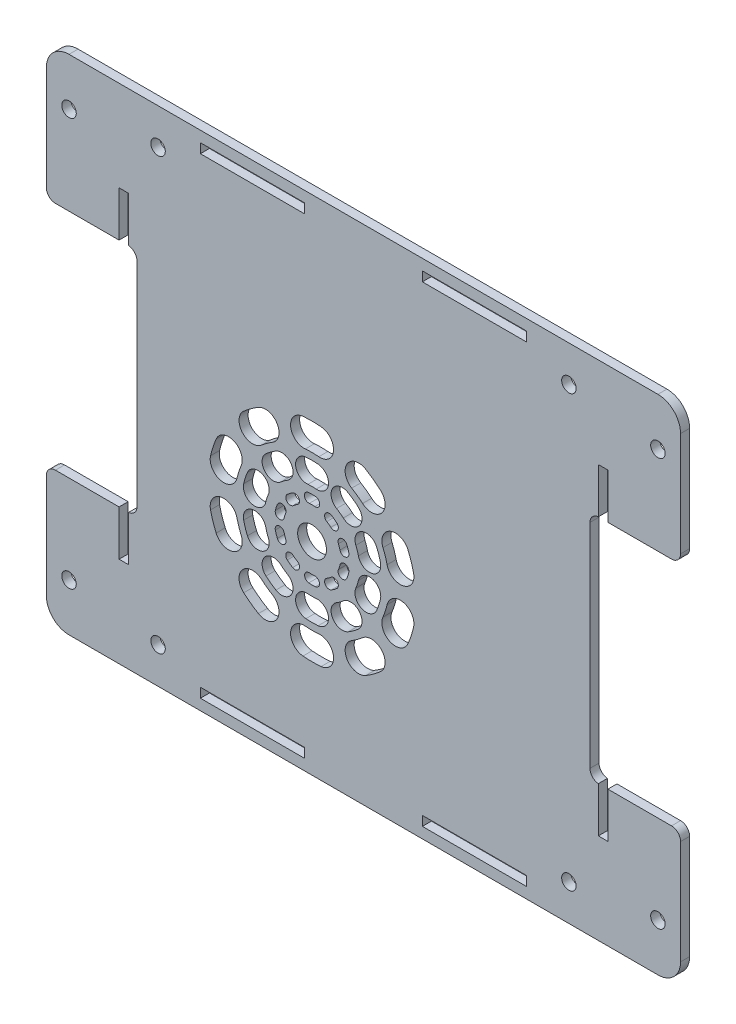
SolidWorks part; units mm, degrees
ref_plane "前视基准面" through (0, 0, 0) normal (0, 0, 1) x (1, 0, 0)
ref_plane "上视基准面" through (0, 0, 0) normal (0, 1, 0) x (1, 0, 0)
ref_plane "右视基准面" through (0, 0, 0) normal (1, 0, 0) x (0, 0, -1)
sketch "草图1" plane through (0, 0, 0) normal (0, 0, 1) x (1, 0, 0)
  line L1 (-70, 55.5) -> (70, 55.5)
  line L2 (-70, 55.5) -> (-70, -55.5)
  line L3 (-70, -55.5) -> (70, -55.5)
  line L4 (70, 55.5) -> (70, -55.5)
  line L5 (-70, 55.5) -> (70, -55.5) construction
  line L6 (-70, -55.5) -> (70, 55.5) construction
  point P0 (0, 0)
  dimension "D1" = 111
  dimension "D2" = 140
extrude "凸台-拉伸1" add sketch "草图1" along normal blind 2
sketch "草图2" plane through (0, 0, 0) normal (0, 0, -1) x (-1, 0, 0)
  circle A0 centre (-45.35, -47.55) radius 1.6
  circle A1 centre (45.35, -47.55) radius 1.6
  circle A2 centre (45.35, 47.55) radius 1.6
  circle A3 centre (-45.35, 47.55) radius 1.6
  dimension "D2" = 3.2
  dimension "D1" = 45.35
  dimension "D3" = 47.55
  dimension "D4" = 2
  dimension "D5" = 2
extrude "切除-拉伸1" cut sketch "草图2" against normal through all
sketch "草图3" plane through (0, 0, 0) normal (0, 0, -1) x (-1, 0, 0)
  line L0 (0, 0) -> (0, -29.5446) construction
  line L1 (0, 0) -> (30.314, 0) construction
  line L3 (-53.95, 35.5) -> (-51.85, 35.5)
  line L4 (-53.95, 35.5) -> (-53.95, 12.5)
  line L5 (-53.95, 12.5) -> (-51.85, 12.5)
  line L6 (-51.85, 35.5) -> (-51.85, 12.5)
  line L7 (-53.95, -12.5) -> (-51.85, -12.5)
  line L8 (-53.95, -12.5) -> (-53.95, -35.5)
  line L9 (-53.95, -35.5) -> (-51.85, -35.5)
  line L10 (-51.85, -12.5) -> (-51.85, -35.5)
  line L11 (70, -55.5) -> (-70, -55.5) construction
  line L12 (-70, 55.5) -> (70, 55.5) construction
  line L13 (51.85, -12.5) -> (51.85, -35.5)
  line L14 (53.95, -35.5) -> (51.85, -35.5)
  line L15 (53.95, -12.5) -> (53.95, -35.5)
  line L16 (53.95, -12.5) -> (51.85, -12.5)
  line L17 (51.85, 35.5) -> (51.85, 12.5)
  line L18 (53.95, 12.5) -> (51.85, 12.5)
  line L19 (53.95, 35.5) -> (53.95, 12.5)
  line L20 (53.95, 35.5) -> (51.85, 35.5)
  line L21 (-70, -55.5) -> (-70, 55.5) construction
  line L22 (-36, -51) -> (-13, -51)
  line L23 (-36, -51) -> (-36, -53.1)
  line L24 (-36, -53.1) -> (-13, -53.1)
  line L25 (-13, -51) -> (-13, -53.1)
  line L26 (13, -51) -> (36, -51)
  line L27 (13, -51) -> (13, -53.1)
  line L28 (13, -53.1) -> (36, -53.1)
  line L29 (36, -51) -> (36, -53.1)
  line L30 (70, 55.5) -> (70, -55.5) construction
  line L31 (36, 51) -> (36, 53.1)
  line L32 (13, 53.1) -> (36, 53.1)
  line L33 (13, 51) -> (13, 53.1)
  line L34 (13, 51) -> (36, 51)
  line L35 (-13, 51) -> (-13, 53.1)
  line L36 (-36, 53.1) -> (-13, 53.1)
  line L37 (-36, 51) -> (-36, 53.1)
  line L38 (-36, 51) -> (-13, 51)
  point P16 (-52.9, 35.5)
  dimension "D1" = 2.1
  dimension "D2" = 2.1
  dimension "D3" = 51.85
  dimension "D4" = 23
  dimension "D5" = 23
  dimension "D6" = 20
  dimension "D7" = 20
  dimension "D8" = 51
  dimension "D9" = 2.1
  dimension "D10" = 2.1
  dimension "D11" = 23
  dimension "D12" = 23
  dimension "D13" = 34
  dimension "D14" = 34
extrude "切除-拉伸2" cut sketch "草图3" against normal through all
sketch "草图4" plane through (0, 0, 2) normal (0, 0, 1) x (1, 0, 0)
  line L0 (-70, -55.5) -> (70, -55.5) construction
  line L2 (-13.0931, 9.1239) -> (-11.35, -10.8) construction
  line L3 (-11.35, -10.8) -> (-9.6069, 9.1239) construction
  line L4 (-11.35, -10.8) -> (-11.35, 9.2) construction
  line L5 (-70, 55.5) -> (-70, -55.5) construction
  line L7 (-11.35, -10.8) -> (8.65, -10.8) construction
  circle A0 centre (-11.35, -10.8) radius 20 construction
  arc A1 (-13.0931, 9.1239) -> (-9.6069, 9.1239) centre (-11.35, -10.8) cw construction
  arc A2 (-9.3454, 12.1125) -> (-13.3546, 12.1125) centre (-11.35, -10.8) ccw
  arc A3 (-9.8684, 6.1353) -> (-12.8316, 6.1353) centre (-11.35, -10.8) ccw
  arc A4 (-9.8684, 6.1353) -> (-9.3454, 12.1125) centre (-9.6069, 9.1239) ccw
  arc A5 (-13.3546, 12.1125) -> (-12.8316, 6.1353) centre (-13.0931, 9.1239) ccw
  arc A6 (-10.217, 2.1505) -> (-12.483, 2.1505) centre (-11.35, -10.8) ccw construction
  arc A7 (-9.9991, 4.641) -> (-12.7009, 4.641) centre (-11.35, -10.8) ccw
  arc A8 (-10.4349, -0.34) -> (-12.2651, -0.34) centre (-11.35, -10.8) ccw
  arc A9 (-10.4349, -0.34) -> (-9.9991, 4.641) centre (-10.217, 2.1505) ccw
  arc A10 (-12.7009, 4.641) -> (-12.2651, -0.34) centre (-12.483, 2.1505) ccw
  arc A11 (-12.0472, -2.8304) -> (-10.6528, -2.8304) centre (-11.35, -10.8) cw construction
  arc A12 (-10.5656, -1.8342) -> (-12.1344, -1.8342) centre (-11.35, -10.8) ccw
  arc A13 (-10.7399, -3.8266) -> (-11.9601, -3.8266) centre (-11.35, -10.8) ccw
  arc A14 (-10.7399, -3.8266) -> (-10.5656, -1.8342) centre (-10.6528, -2.8304) ccw
  arc A15 (-12.1344, -1.8342) -> (-11.9601, -3.8266) centre (-12.0472, -2.8304) ccw
  arc A16 (-1.0492, 6.3433) -> (1.7712, 4.2942) centre (-11.35, -10.8) cw construction
  arc A21 (3.7394, 6.5583) -> (0.4959, 8.9148) centre (-11.35, -10.8) ccw
  arc A26 (-0.197, 2.0301) -> (-2.5944, 3.7718) centre (-11.35, -10.8) ccw
  arc A31 (-0.197, 2.0301) -> (3.7394, 6.5583) centre (1.7712, 4.2942) ccw
  arc A36 (0.4959, 8.9148) -> (-2.5944, 3.7718) centre (-1.0492, 6.3433) ccw
  arc A41 (-2.8212, -0.9888) -> (-4.6545, 0.3432) centre (-11.35, -10.8) ccw construction
  arc A46 (-1.1811, 0.898) -> (-3.3669, 2.4861) centre (-11.35, -10.8) ccw
  arc A51 (-4.4614, -2.8755) -> (-5.9421, -1.7997) centre (-11.35, -10.8) ccw
  arc A56 (-4.4614, -2.8755) -> (-1.1811, 0.898) centre (-2.8212, -0.9888) ccw
  arc A62 (-3.3669, 2.4861) -> (-5.9421, -1.7997) centre (-4.6545, 0.3432) ccw
  arc A63 (-7.5793, -4.5246) -> (-6.5469, -5.2747) centre (-11.35, -10.8) cw construction
  arc A64 (-5.8909, -4.52) -> (-7.0643, -3.6674) centre (-11.35, -10.8) ccw
  arc A65 (-7.203, -6.0294) -> (-8.0944, -5.3817) centre (-11.35, -10.8) ccw
  arc A66 (-7.203, -6.0294) -> (-5.8909, -4.52) centre (-6.5469, -5.2747) ccw
  arc A67 (-7.0643, -3.6674) -> (-8.0944, -5.3817) centre (-7.5793, -4.5246) ccw
  arc A68 (7.0601, -2.9854) -> (8.1374, -6.301) centre (-11.35, -10.8) cw construction
  arc A69 (11.0605, -5.6261) -> (9.8216, -1.8132) centre (-11.35, -10.8) ccw
  arc A70 (5.2143, -6.9758) -> (4.2986, -4.1576) centre (-11.35, -10.8) ccw
  arc A71 (5.2143, -6.9758) -> (11.0605, -5.6261) centre (8.1374, -6.301) ccw
  arc A72 (9.8216, -1.8132) -> (4.2986, -4.1576) centre (7.0601, -2.9854) ccw
  arc A73 (1.3168, -7.8756) -> (0.6166, -5.7205) centre (-11.35, -10.8) ccw construction
  arc A74 (3.7527, -7.3133) -> (2.9178, -4.7437) centre (-11.35, -10.8) ccw
  arc A75 (-1.1191, -8.438) -> (-1.6847, -6.6973) centre (-11.35, -10.8) ccw
  arc A76 (-1.1191, -8.438) -> (3.7527, -7.3133) centre (1.3168, -7.8756) ccw
  arc A77 (2.9178, -4.7437) -> (-1.6847, -6.6973) centre (0.6166, -5.7205) ccw
  arc A78 (-4.6109, -7.9394) -> (-4.2165, -9.1531) centre (-11.35, -10.8) cw construction
  arc A79 (-3.2421, -8.9282) -> (-3.6904, -7.5487) centre (-11.35, -10.8) ccw
  arc A80 (-5.1909, -9.3781) -> (-5.5314, -8.3301) centre (-11.35, -10.8) ccw
  arc A81 (-5.1909, -9.3781) -> (-3.2421, -8.9282) centre (-4.2165, -9.1531) ccw
  arc A82 (-3.6904, -7.5487) -> (-5.5314, -8.3301) centre (-4.6109, -7.9394) ccw
  arc A83 (8.1374, -15.299) -> (7.0601, -18.6146) centre (-11.35, -10.8) cw construction
  arc A84 (9.8216, -19.7868) -> (11.0605, -15.9739) centre (-11.35, -10.8) ccw
  arc A85 (4.2986, -17.4424) -> (5.2143, -14.6242) centre (-11.35, -10.8) ccw
  arc A86 (4.2986, -17.4424) -> (9.8216, -19.7868) centre (7.0601, -18.6146) ccw
  arc A87 (11.0605, -15.9739) -> (5.2143, -14.6242) centre (8.1374, -15.299) ccw
  arc A88 (0.6166, -15.8795) -> (1.3168, -13.7244) centre (-11.35, -10.8) ccw construction
  arc A89 (2.9178, -16.8563) -> (3.7527, -14.2867) centre (-11.35, -10.8) ccw
  arc A90 (-1.6847, -14.9027) -> (-1.1191, -13.162) centre (-11.35, -10.8) ccw
  arc A91 (-1.6847, -14.9027) -> (2.9178, -16.8563) centre (0.6166, -15.8795) ccw
  arc A92 (3.7527, -14.2867) -> (-1.1191, -13.162) centre (1.3168, -13.7244) ccw
  arc A93 (-4.2165, -12.4469) -> (-4.6109, -13.6606) centre (-11.35, -10.8) cw construction
  arc A94 (-3.6904, -14.0513) -> (-3.2421, -12.6718) centre (-11.35, -10.8) ccw
  arc A95 (-5.5314, -13.2699) -> (-5.1909, -12.2219) centre (-11.35, -10.8) ccw
  arc A96 (-5.5314, -13.2699) -> (-3.6904, -14.0513) centre (-4.6109, -13.6606) ccw
  arc A97 (-3.2421, -12.6718) -> (-5.1909, -12.2219) centre (-4.2165, -12.4469) ccw
  arc A98 (1.7712, -25.8942) -> (-1.0492, -27.9433) centre (-11.35, -10.8) cw construction
  arc A99 (0.4959, -30.5148) -> (3.7394, -28.1583) centre (-11.35, -10.8) ccw
  arc A100 (-2.5944, -25.3718) -> (-0.197, -23.6301) centre (-11.35, -10.8) ccw
  arc A101 (-2.5944, -25.3718) -> (0.4959, -30.5148) centre (-1.0492, -27.9433) ccw
  arc A102 (3.7394, -28.1583) -> (-0.197, -23.6301) centre (1.7712, -25.8942) ccw
  arc A103 (-4.6545, -21.9432) -> (-2.8212, -20.6112) centre (-11.35, -10.8) ccw construction
  arc A104 (-3.3669, -24.0861) -> (-1.1811, -22.498) centre (-11.35, -10.8) ccw
  arc A105 (-5.9421, -19.8003) -> (-4.4614, -18.7245) centre (-11.35, -10.8) ccw
  arc A106 (-5.9421, -19.8003) -> (-3.3669, -24.0861) centre (-4.6545, -21.9432) ccw
  arc A107 (-1.1811, -22.498) -> (-4.4614, -18.7245) centre (-2.8212, -20.6112) ccw
  arc A108 (-6.5469, -16.3253) -> (-7.5793, -17.0754) centre (-11.35, -10.8) cw construction
  arc A109 (-7.0643, -17.9326) -> (-5.8909, -17.08) centre (-11.35, -10.8) ccw
  arc A110 (-8.0944, -16.2183) -> (-7.203, -15.5706) centre (-11.35, -10.8) ccw
  arc A111 (-8.0944, -16.2183) -> (-7.0643, -17.9326) centre (-7.5793, -17.0754) ccw
  arc A112 (-5.8909, -17.08) -> (-7.203, -15.5706) centre (-6.5469, -16.3253) ccw
  arc A113 (-9.6069, -30.7239) -> (-13.0931, -30.7239) centre (-11.35, -10.8) cw construction
  arc A114 (-13.3546, -33.7125) -> (-9.3454, -33.7125) centre (-11.35, -10.8) ccw
  arc A115 (-12.8316, -27.7353) -> (-9.8684, -27.7353) centre (-11.35, -10.8) ccw
  arc A116 (-12.8316, -27.7353) -> (-13.3546, -33.7125) centre (-13.0931, -30.7239) ccw
  arc A117 (-9.3454, -33.7125) -> (-9.8684, -27.7353) centre (-9.6069, -30.7239) ccw
  arc A118 (-12.483, -23.7505) -> (-10.217, -23.7505) centre (-11.35, -10.8) ccw construction
  arc A119 (-12.7009, -26.241) -> (-9.9991, -26.241) centre (-11.35, -10.8) ccw
  arc A120 (-12.2651, -21.26) -> (-10.4349, -21.26) centre (-11.35, -10.8) ccw
  arc A121 (-12.2651, -21.26) -> (-12.7009, -26.241) centre (-12.483, -23.7505) ccw
  arc A122 (-9.9991, -26.241) -> (-10.4349, -21.26) centre (-10.217, -23.7505) ccw
  arc A123 (-10.7119, -18.0933) -> (-11.9881, -18.0933) centre (-11.35, -10.8) cw construction
  arc A124 (-12.0752, -19.0895) -> (-10.6248, -19.0895) centre (-11.35, -10.8) ccw
  arc A125 (-11.9009, -17.0971) -> (-10.7991, -17.0971) centre (-11.35, -10.8) ccw
  arc A126 (-11.9009, -17.0971) -> (-12.0752, -19.0895) centre (-11.9881, -18.0933) ccw
  arc A127 (-10.6248, -19.0895) -> (-10.7991, -17.0971) centre (-10.7119, -18.0933) ccw
  arc A128 (-21.6508, -27.9433) -> (-24.4712, -25.8942) centre (-11.35, -10.8) cw construction
  arc A129 (-26.4394, -28.1583) -> (-23.1959, -30.5148) centre (-11.35, -10.8) ccw
  arc A130 (-22.503, -23.6301) -> (-20.1056, -25.3718) centre (-11.35, -10.8) ccw
  arc A131 (-22.503, -23.6301) -> (-26.4394, -28.1583) centre (-24.4712, -25.8942) ccw
  arc A132 (-23.1959, -30.5148) -> (-20.1056, -25.3718) centre (-21.6508, -27.9433) ccw
  arc A133 (-19.8788, -20.6112) -> (-18.0455, -21.9432) centre (-11.35, -10.8) ccw construction
  arc A134 (-21.5189, -22.498) -> (-19.3331, -24.0861) centre (-11.35, -10.8) ccw
  arc A135 (-18.2386, -18.7245) -> (-16.7579, -19.8003) centre (-11.35, -10.8) ccw
  arc A136 (-18.2386, -18.7245) -> (-21.5189, -22.498) centre (-19.8788, -20.6112) ccw
  arc A137 (-19.3331, -24.0861) -> (-16.7579, -19.8003) centre (-18.0455, -21.9432) ccw
  arc A138 (-15.1207, -17.0754) -> (-16.1531, -16.3253) centre (-11.35, -10.8) cw construction
  arc A139 (-16.8091, -17.08) -> (-15.6357, -17.9326) centre (-11.35, -10.8) ccw
  arc A140 (-15.497, -15.5706) -> (-14.6056, -16.2183) centre (-11.35, -10.8) ccw
  arc A141 (-15.497, -15.5706) -> (-16.8091, -17.08) centre (-16.1531, -16.3253) ccw
  arc A142 (-15.6357, -17.9326) -> (-14.6056, -16.2183) centre (-15.1207, -17.0754) ccw
  arc A143 (-29.7601, -18.6146) -> (-30.8374, -15.299) centre (-11.35, -10.8) cw construction
  arc A144 (-33.7605, -15.9739) -> (-32.5216, -19.7868) centre (-11.35, -10.8) ccw
  arc A145 (-27.9143, -14.6242) -> (-26.9986, -17.4424) centre (-11.35, -10.8) ccw
  arc A146 (-27.9143, -14.6242) -> (-33.7605, -15.9739) centre (-30.8374, -15.299) ccw
  arc A147 (-32.5216, -19.7868) -> (-26.9986, -17.4424) centre (-29.7601, -18.6146) ccw
  arc A148 (-24.0168, -13.7244) -> (-23.3166, -15.8795) centre (-11.35, -10.8) ccw construction
  arc A149 (-26.4527, -14.2867) -> (-25.6178, -16.8563) centre (-11.35, -10.8) ccw
  arc A150 (-21.5809, -13.162) -> (-21.0153, -14.9027) centre (-11.35, -10.8) ccw
  arc A151 (-21.5809, -13.162) -> (-26.4527, -14.2867) centre (-24.0168, -13.7244) ccw
  arc A152 (-25.6178, -16.8563) -> (-21.0153, -14.9027) centre (-23.3166, -15.8795) ccw
  arc A153 (-18.0891, -13.6606) -> (-18.4835, -12.4469) centre (-11.35, -10.8) cw construction
  arc A154 (-19.4579, -12.6718) -> (-19.0096, -14.0513) centre (-11.35, -10.8) ccw
  arc A155 (-17.5091, -12.2219) -> (-17.1686, -13.2699) centre (-11.35, -10.8) ccw
  arc A156 (-17.5091, -12.2219) -> (-19.4579, -12.6718) centre (-18.4835, -12.4469) ccw
  arc A157 (-19.0096, -14.0513) -> (-17.1686, -13.2699) centre (-18.0891, -13.6606) ccw
  arc A158 (-30.8374, -6.301) -> (-29.7601, -2.9854) centre (-11.35, -10.8) cw construction
  arc A159 (-32.5216, -1.8132) -> (-33.7605, -5.6261) centre (-11.35, -10.8) ccw
  arc A160 (-26.9986, -4.1576) -> (-27.9143, -6.9758) centre (-11.35, -10.8) ccw
  arc A161 (-26.9986, -4.1576) -> (-32.5216, -1.8132) centre (-29.7601, -2.9854) ccw
  arc A162 (-33.7605, -5.6261) -> (-27.9143, -6.9758) centre (-30.8374, -6.301) ccw
  arc A163 (-23.3166, -5.7205) -> (-24.0168, -7.8756) centre (-11.35, -10.8) ccw construction
  arc A164 (-25.6178, -4.7437) -> (-26.4527, -7.3133) centre (-11.35, -10.8) ccw
  arc A165 (-21.0153, -6.6973) -> (-21.5809, -8.438) centre (-11.35, -10.8) ccw
  arc A166 (-21.0153, -6.6973) -> (-25.6178, -4.7437) centre (-23.3166, -5.7205) ccw
  arc A167 (-26.4527, -7.3133) -> (-21.5809, -8.438) centre (-24.0168, -7.8756) ccw
  arc A168 (-18.4835, -9.1531) -> (-18.0891, -7.9394) centre (-11.35, -10.8) cw construction
  arc A169 (-19.0096, -7.5487) -> (-19.4579, -8.9282) centre (-11.35, -10.8) ccw
  arc A170 (-17.1686, -8.3301) -> (-17.5091, -9.3781) centre (-11.35, -10.8) ccw
  arc A171 (-17.1686, -8.3301) -> (-19.0096, -7.5487) centre (-18.0891, -7.9394) ccw
  arc A172 (-19.4579, -8.9282) -> (-17.5091, -9.3781) centre (-18.4835, -9.1531) ccw
  arc A173 (-24.4712, 4.2942) -> (-21.6508, 6.3433) centre (-11.35, -10.8) cw construction
  arc A174 (-23.1959, 8.9148) -> (-26.4394, 6.5583) centre (-11.35, -10.8) ccw
  arc A175 (-20.1056, 3.7718) -> (-22.503, 2.0301) centre (-11.35, -10.8) ccw
  arc A176 (-20.1056, 3.7718) -> (-23.1959, 8.9148) centre (-21.6508, 6.3433) ccw
  arc A177 (-26.4394, 6.5583) -> (-22.503, 2.0301) centre (-24.4712, 4.2942) ccw
  arc A178 (-18.0455, 0.3432) -> (-19.8788, -0.9888) centre (-11.35, -10.8) ccw construction
  arc A179 (-19.3331, 2.4861) -> (-21.5189, 0.898) centre (-11.35, -10.8) ccw
  arc A180 (-16.7579, -1.7997) -> (-18.2386, -2.8755) centre (-11.35, -10.8) ccw
  arc A181 (-16.7579, -1.7997) -> (-19.3331, 2.4861) centre (-18.0455, 0.3432) ccw
  arc A182 (-21.5189, 0.898) -> (-18.2386, -2.8755) centre (-19.8788, -0.9888) ccw
  arc A183 (-16.1531, -5.2747) -> (-15.1207, -4.5246) centre (-11.35, -10.8) cw construction
  arc A184 (-15.6357, -3.6674) -> (-16.8091, -4.52) centre (-11.35, -10.8) ccw
  arc A185 (-14.6056, -5.3817) -> (-15.497, -6.0294) centre (-11.35, -10.8) ccw
  arc A186 (-14.6056, -5.3817) -> (-15.6357, -3.6674) centre (-15.1207, -4.5246) ccw
  arc A187 (-16.8091, -4.52) -> (-15.497, -6.0294) centre (-16.1531, -5.2747) ccw
  circle A188 centre (-11.35, -10.8) radius 3.181
  point P8 (-11.35, 9.2)
  point P19 (-11.35, 2.2)
  point P27 (-11.35, -2.8)
  point P37 (0.4057, 5.3803)
  point P44 (-3.7088, -0.2828)
  point P52 (-7.0467, -4.8771)
  point P59 (7.6711, -4.6197)
  point P66 (1.0137, -6.7828)
  point P73 (-4.3872, -8.5376)
  point P80 (7.6711, -16.9803)
  point P87 (1.0137, -14.8172)
  point P94 (-4.3872, -13.0624)
  point P101 (0.4057, -26.9803)
  point P108 (-3.7088, -21.3172)
  point P115 (-7.0467, -16.7229)
  point P122 (-11.35, -30.8)
  point P129 (-11.35, -23.8)
  point P136 (-11.35, -18.1211)
  point P143 (-23.1057, -26.9803)
  point P150 (-18.9912, -21.3172)
  point P157 (-15.6533, -16.7229)
  point P164 (-30.3711, -16.9803)
  point P171 (-23.7137, -14.8172)
  point P178 (-18.3128, -13.0624)
  point P185 (-30.3711, -4.6197)
  point P192 (-23.7137, -6.7828)
  point P199 (-18.3128, -8.5376)
  point P206 (-23.1057, 5.3803)
  point P213 (-18.9912, -0.2828)
  point P220 (-15.6533, -4.8771)
  point P225 (-11.35, -10.8)
  dimension "D3" = 40
  dimension "D5" = 3
  dimension "D6" = 2.5
  dimension "D8" = 5
  dimension "D7" = 7
  dimension "D9" = 1
  dimension "D10" = 1
  dimension "D1" = 44.7
  dimension "D2" = 58.65
  dimension "D4" = 5
extrude "切除-拉伸4" cut sketch "草图4" against normal blind 10
fillet "圆角1" radius 5 4 edges at (70, -55.5, 1) (-70, -55.5, 1) (-70, 55.5, 1) (70, 55.5, 1)
sketch "草图5" plane through (0, 0, 0) normal (0, 0, -1) x (-1, 0, 0)
  line L1 (65, -45) -> (-65, -45) construction
  line L2 (65, -45) -> (65, 45) construction
  line L3 (65, 45) -> (-65, 45) construction
  line L4 (-65, -45) -> (-65, 45) construction
  line L5 (65, -45) -> (-65, 45) construction
  line L6 (65, 45) -> (-65, -45) construction
  circle A0 centre (-65, 45) radius 1.6
  circle A1 centre (65, 45) radius 1.6
  circle A2 centre (65, -45) radius 1.6
  circle A3 centre (-65, -45) radius 1.6
  point P0 (0, 0)
  dimension "D1" = 3.2
  dimension "D2" = 130
  dimension "D3" = 90
extrude "切除-拉伸5" cut sketch "草图5" against normal blind 10
sketch "草图6" plane through (0, 0, 0) normal (0, 0, -1) x (-1, 0, 0)
  line L0 (70, 50.5) -> (70, -50.5) construction
  line L1 (70, 25.5) -> (50, 25.5)
  line L2 (70, 25.5) -> (70, -25.5)
  line L3 (70, -25.5) -> (50, -25.5)
  line L4 (50, 25.5) -> (50, -25.5)
  line L5 (-70, 0) -> (70, 0) construction
  line L6 (-70, -50.5) -> (-70, 50.5) construction
  line L7 (-65, 55.5) -> (65, 55.5) construction
  point P11 (70, 0)
  dimension "D1" = 30
  dimension "D2" = 20
extrude "切除-拉伸6" cut sketch "草图6" against normal blind 10
fillet "圆角2" radius 2 4 edges at (-70, -25.5, 1) (-50, -25.5, 1) (-50, 25.5, 1) (-70, 25.5, 1)
ref_plane "基准面1" through (0, 0, 0) normal (-1, 0, 0) x (0, 0, 1)
mirror "镜向1" about plane through (0, 0, 0) normal (-1, 0, 0) of "切除-拉伸6"
fillet "圆角3" radius 2 4 edges at (50, -25.5, 1) (70, -25.5, 1) (50, 25.5, 1) (70, 25.5, 1)
